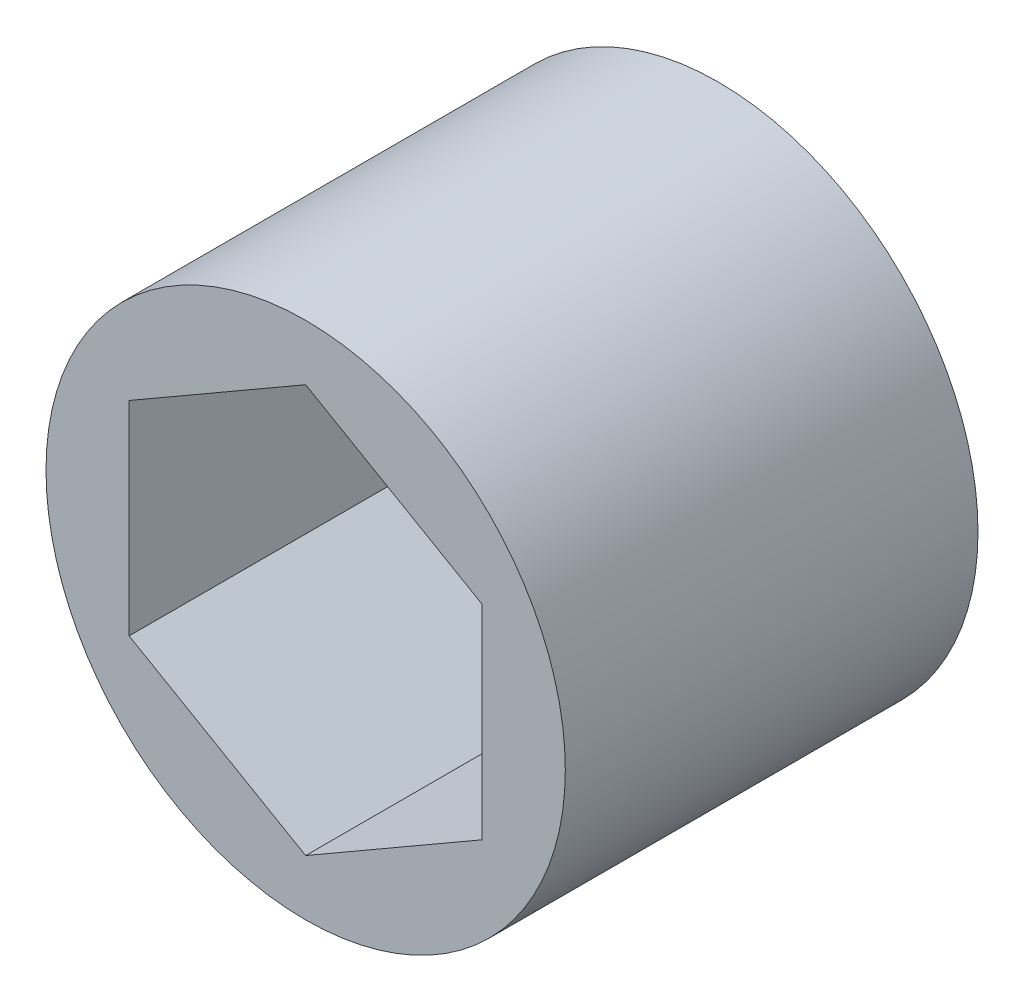
SolidWorks part; units mm, degrees
material "PET"
ref_plane "Front Plane" through (0, 0, 0) normal (0, 0, 1) x (1, 0, 0)
ref_plane "Top Plane" through (0, 0, 0) normal (0, 1, 0) x (1, 0, 0)
ref_plane "Right Plane" through (0, 0, 0) normal (1, 0, 0) x (0, 0, -1)
sketch "Sketch1" plane through (0, 0, 0) normal (0, 0, 1) x (1, 0, 0)
  line L1 (0, 7.479) -> (-6.477, 3.7395)
  line L2 (-6.477, 3.7395) -> (-6.477, -3.7395)
  line L3 (-6.477, -3.7395) -> (0, -7.479)
  line L4 (0, -7.479) -> (6.477, -3.7395)
  line L5 (6.477, -3.7395) -> (6.477, 3.7395)
  line L6 (6.477, 3.7395) -> (0, 7.479)
  circle A0 centre (0, 0) radius 6.477 construction
  circle A1 centre (0, 0) radius 9.525
  dimension "D1" = 12.954
  dimension "D2" = 19.05
extrude "Boss-Extrude1" add sketch "Sketch1" along normal mid plane 15.1384
